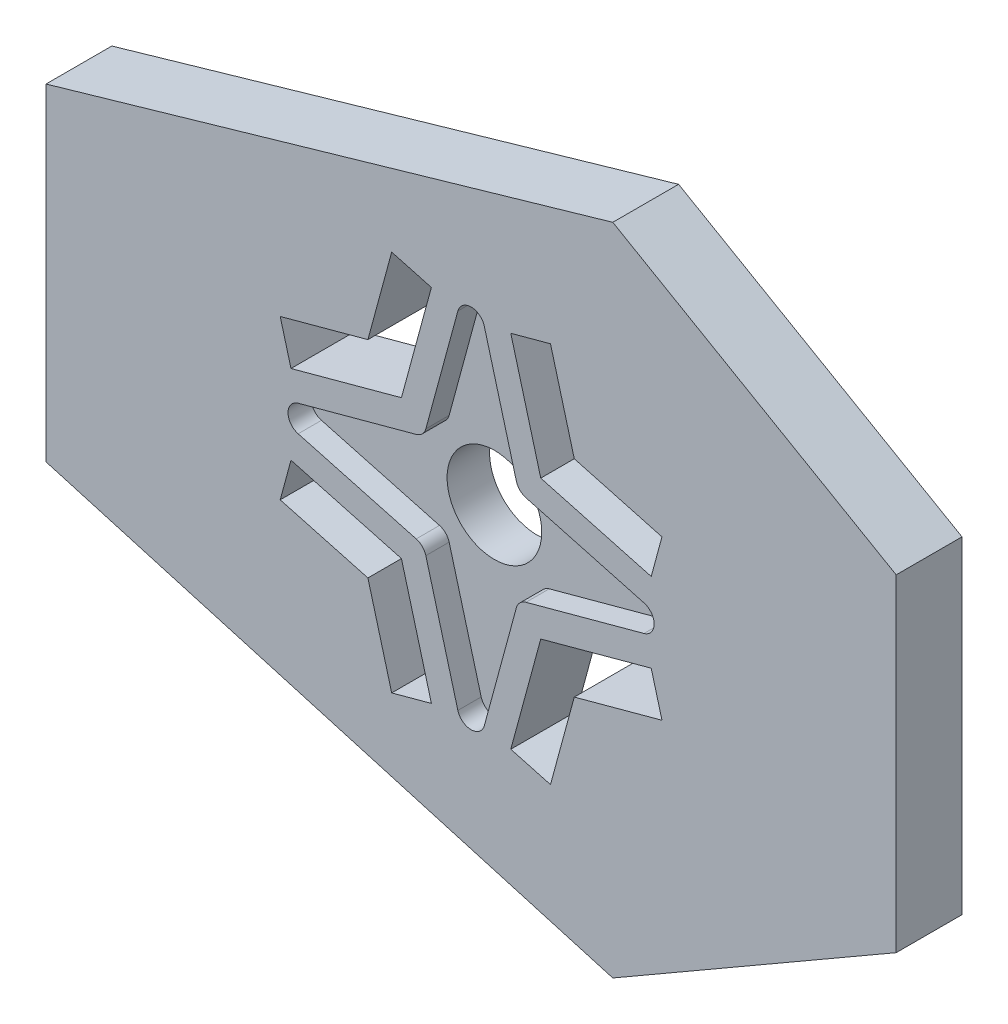
SolidWorks part; units mm, degrees
ref_plane "Front Plane" through (0, 0, 0) normal (0, 0, 1) x (1, 0, 0)
ref_plane "Top Plane" through (0, 0, 0) normal (0, 1, 0) x (1, 0, 0)
ref_plane "Right Plane" through (0, 0, 0) normal (1, 0, 0) x (0, 0, -1)
sketch "Sketch1" plane through (0, 0, 0) normal (0, 0, 1) x (1, 0, 0)
  line L0 (5.1833, -23.8638) -> (-36.15, -11.9319) construction
  line L1 (-36.15, 11.9319) -> (-36.15, -11.9319) construction
  line L2 (-36.15, 11.9319) -> (5.1833, 23.8638) construction
  line L3 (25.85, 11.9319) -> (5.1833, 23.8638) construction
  line L4 (25.85, -11.9319) -> (25.85, 11.9319) construction
  line L5 (5.1833, -23.8638) -> (25.85, -11.9319) construction
  line L6 (5.1833, -23.8638) -> (-36.15, -11.9319)
  line L7 (-36.15, 11.9319) -> (-36.15, -11.9319)
  line L8 (-36.15, 11.9319) -> (5.1833, 23.8638)
  line L9 (25.85, 11.9319) -> (5.1833, 23.8638)
  line L10 (25.85, -11.9319) -> (25.85, 11.9319)
  line L11 (5.1833, -23.8638) -> (25.85, -11.9319)
  line L20 (-4.1849, -12.6118) -> (-1.8501, -4.0033)
  line L21 (-1.1467, -3.2999) -> (7.4618, -0.9651)
  line L22 (7.4618, 0.9651) -> (-1.1467, 3.2999)
  line L23 (-1.8501, 4.0033) -> (-4.1849, 12.6118)
  line L24 (-6.1151, 12.6118) -> (-8.4499, 4.0033)
  line L25 (-9.1533, 3.2999) -> (-17.7618, 0.9651)
  line L26 (-17.7618, -0.9651) -> (-9.1533, -3.2999)
  line L27 (-8.4499, -4.0033) -> (-6.1151, -12.6118)
  line L28 (-4.1849, -12.6118) -> (-1.8501, -4.0033)
  line L29 (-1.1467, -3.2999) -> (7.4618, -0.9651)
  line L30 (7.4618, 0.9651) -> (-1.1467, 3.2999)
  line L31 (-1.8501, 4.0033) -> (-4.1849, 12.6118)
  line L32 (-6.1151, 12.6118) -> (-8.4499, 4.0033)
  line L33 (-9.1533, 3.2999) -> (-17.7618, 0.9651)
  line L34 (-17.7618, -0.9651) -> (-9.1533, -3.2999)
  line L35 (-8.4499, -4.0033) -> (-6.1151, -12.6118)
  circle A0 centre (-5.15, 0) radius 3.45 construction
  circle A1 centre (-5.15, 0) radius 3.45
  arc A8 (-1.1467, -3.2999) -> (-1.8501, -4.0033) centre (-0.8849, -4.2651) ccw
  arc A9 (7.4618, -0.9651) -> (7.4618, 0.9651) centre (7.2, 0) ccw
  arc A10 (-1.8501, 4.0033) -> (-1.1467, 3.2999) centre (-0.8849, 4.2651) ccw
  arc A11 (-4.1849, 12.6118) -> (-6.1151, 12.6118) centre (-5.15, 12.35) ccw
  arc A12 (-9.1533, 3.2999) -> (-8.4499, 4.0033) centre (-9.4151, 4.2651) ccw
  arc A13 (-17.7618, 0.9651) -> (-17.7618, -0.9651) centre (-17.5, 0) ccw
  arc A14 (-8.4499, -4.0033) -> (-9.1533, -3.2999) centre (-9.4151, -4.2651) ccw
  arc A15 (-6.1151, -12.6118) -> (-4.1849, -12.6118) centre (-5.15, -12.35) ccw
  arc A16 (-1.1467, -3.2999) -> (-1.8501, -4.0033) centre (-0.8849, -4.2651) ccw
  arc A17 (7.4618, -0.9651) -> (7.4618, 0.9651) centre (7.2, 0) ccw
  arc A18 (-1.8501, 4.0033) -> (-1.1467, 3.2999) centre (-0.8849, 4.2651) ccw
  arc A19 (-4.1849, 12.6118) -> (-6.1151, 12.6118) centre (-5.15, 12.35) ccw
  arc A20 (-9.1533, 3.2999) -> (-8.4499, 4.0033) centre (-9.4151, 4.2651) ccw
  arc A21 (-17.7618, 0.9651) -> (-17.7618, -0.9651) centre (-17.5, 0) ccw
  arc A22 (-8.4499, -4.0033) -> (-9.1533, -3.2999) centre (-9.4151, -4.2651) ccw
  arc A23 (-6.1151, -12.6118) -> (-4.1849, -12.6118) centre (-5.15, -12.35) ccw
  dimension "D1" = 0
extrude "Boss-Extrude1" add sketch "Sketch1" along normal up to surface (3.1 mm away) contours L8 L9 L10 L11 L6 L7 | A1
extrude "Boss-Extrude2" add sketch "Sketch1<3>" along normal up to surface (4.8 mm away) contours L6 L11 L10 L9 L8 L7 A23 L35 A22 L34 A21 L33 A20 L32 A19 L31 A18 L30 A17 L29 A16 L28 region at (-15.2663, -17.1461, 0)
sketch "Sketch1<3>" plane through (0, 0, 0) normal (0, 0, 1) x (1, 0, 0) same geometry as "Sketch1"
sketch "Sketch3" plane through (0, 0, 4.8) normal (0, 0, 1) x (1, 0, 0)
  line L0 (-12.6753, 7.5253) -> (-19.0706, 5.7908) construction
  line L1 (-19.0706, 5.7908) -> (-18.2853, 2.8954) construction
  line L2 (-10.2301, 5.0801) -> (-18.2853, 2.8954) construction
  line L3 (-8.0454, 13.1353) -> (-10.2301, 5.0801) construction
  line L4 (-10.9408, 13.9206) -> (-8.0454, 13.1353) construction
  line L5 (-10.9408, 13.9206) -> (-12.6753, 7.5253) construction
  line L6 (-12.6753, 7.5253) -> (-19.0706, 5.7908)
  line L7 (-19.0706, 5.7908) -> (-18.2853, 2.8954)
  line L8 (-10.2301, 5.0801) -> (-18.2853, 2.8954)
  line L9 (-8.0454, 13.1353) -> (-10.2301, 5.0801)
  line L10 (-10.9408, 13.9206) -> (-8.0454, 13.1353)
  line L11 (-10.9408, 13.9206) -> (-12.6753, 7.5253)
extrude "Cut-Extrude1" cut sketch "Sketch3" against normal through all
sketch "Sketch4" plane through (0, 0, 4.8) normal (0, 0, 1) x (1, 0, 0)
  line L0 (-5.15, 13.35) -> (-5.15, -13.35) construction
  line L1 (-18.5, 0) -> (8.2, 0) construction
  arc A0 (-4.1849, 12.6118) -> (-6.1151, 12.6118) centre (-5.15, 12.35) ccw construction
  arc A1 (-6.1151, -12.6118) -> (-4.1849, -12.6118) centre (-5.15, -12.35) ccw construction
  arc A2 (-17.7618, 0.9651) -> (-17.7618, -0.9651) centre (-17.5, 0) ccw construction
  arc A3 (7.4618, -0.9651) -> (7.4618, 0.9651) centre (7.2, 0) ccw construction
ref_plane "Plane1" through (-5.15, 0, 0) normal (-1, 0, 0) x (0, -1, 0)
ref_plane "Plane2" through (0, 0, 0) normal (0, -1, 0) x (1, 0, 0)
mirror "Mirror1" about plane through (-5.15, 0, 0) normal (-1, 0, 0) of "Cut-Extrude1"
mirror "Mirror2" about plane through (0, 0, 0) normal (0, -1, 0) of "Cut-Extrude1", "Mirror1"
